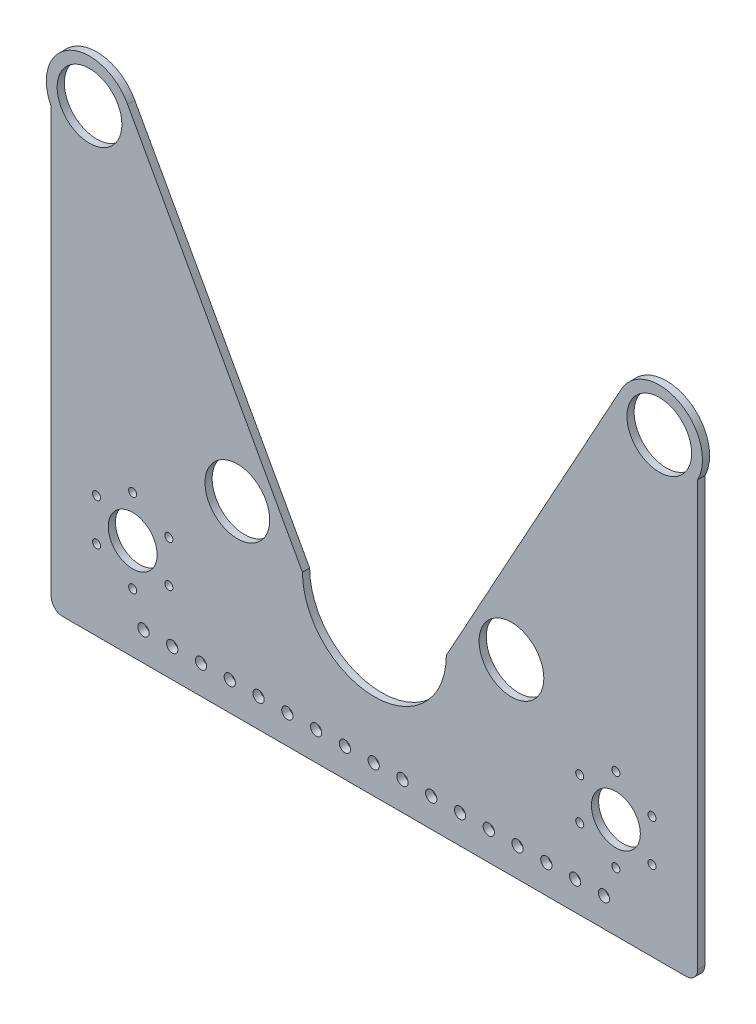
SolidWorks part; units mm, degrees
ref_plane "Front Plane" through (0, 0, 0) normal (0, 0, 1) x (1, 0, 0)
ref_plane "Top Plane" through (0, 0, 0) normal (0, 1, 0) x (1, 0, 0)
ref_plane "Right Plane" through (0, 0, 0) normal (1, 0, 0) x (0, 0, -1)
sketch "Sketch2" plane through (0, 0, 0) normal (0, 0, 1) x (1, 0, 0)
  line L0 (-142.6324, -29.9371) -> (-142.6324, -64.77)
  line L1 (142.6324, 122.4629) -> (142.6324, -29.9371)
  line L3 (31.75, 0) -> (108.9183, 140.209)
  line L4 (0, -1082.0685) -> (0, 1082.0685) construction
  line L5 (-106.68, -44.45) -> (106.68, -44.45) construction
  line L7 (0, -31.75) -> (106.68, -31.75) construction
  line L9 (-31.75, 0) -> (-108.9183, 140.209)
  line L10 (31.75, 0) -> (108.9183, 140.209)
  line L11 (142.6324, -64.77) -> (142.6324, -29.9371)
  line L33 (-106.68, -31.75) -> (0, -31.75) construction
  line L34 (-142.6324, 122.4629) -> (-142.6324, -29.9371)
  line L35 (137.5524, -69.85) -> (-137.5524, -69.85)
  arc A0 (-31.75, 0) -> (31.75, 0) centre (0, 0) ccw
  arc A1 (-108.9183, 140.209) -> (-142.6324, 122.4629) centre (-125.7268, 131.2438) ccw
  circle A2 centre (-60.4845, 12.7) radius 14.2875
  arc A3 (31.75, 0) -> (0, 31.75) centre (0, 0) ccw construction
  arc A4 (0, 31.75) -> (-31.75, 0) centre (0, 0) ccw construction
  arc A5 (137.5524, -69.85) -> (142.6324, -64.77) centre (137.5524, -64.77) ccw
  arc A6 (-137.5524, -69.85) -> (-142.6324, -64.77) centre (-137.5524, -64.77) cw
  circle A7 centre (-125.7268, 131.2438) radius 14.2875
  circle A9 centre (-60.4845, 12.7) radius 19.05 construction
  circle A10 centre (60.4845, 12.7) radius 19.05 construction
  arc A11 (108.9183, 140.209) -> (142.6324, 122.4629) centre (125.7268, 131.2438) cw
  circle A12 centre (125.7268, 131.2438) radius 14.2875
  circle A34 centre (-101.9175, -57.15) radius 2.4892
  arc A40 (-142.6324, 122.4629) -> (-108.9183, 140.209) centre (-125.7268, 131.2438) ccw construction
  arc A41 (142.6324, 122.4629) -> (108.9183, 140.209) centre (125.7268, 131.2438) cw construction
  circle A42 centre (60.4845, 12.7) radius 14.2875
  circle A43 centre (-89.2175, -57.15) radius 2.4892
  circle A44 centre (-76.5175, -57.15) radius 2.4892
  circle A45 centre (-63.8175, -57.15) radius 2.4892
  circle A46 centre (-51.1175, -57.15) radius 2.4892
  circle A47 centre (-38.4175, -57.15) radius 2.4892
  circle A48 centre (-25.7175, -57.15) radius 2.4892
  circle A49 centre (-13.0175, -57.15) radius 2.4892
  circle A50 centre (-0.3175, -57.15) radius 2.4892
  circle A51 centre (12.3825, -57.15) radius 2.4892
  circle A52 centre (25.0825, -57.15) radius 2.4892
  circle A53 centre (37.7825, -57.15) radius 2.4892
  circle A54 centre (50.4825, -57.15) radius 2.4892
  circle A55 centre (63.1825, -57.15) radius 2.4892
  circle A56 centre (75.8825, -57.15) radius 2.4892
  circle A57 centre (88.5825, -57.15) radius 2.4892
  circle A58 centre (101.2825, -57.15) radius 2.4892
  circle A69 centre (-106.68, -25.4) radius 10.795
  circle A70 centre (106.5644, -25.4) radius 10.795
  circle A74 centre (-106.68, -6.985) radius 1.778
  circle A75 centre (-90.7321, -16.1925) radius 1.778
  circle A76 centre (-90.7321, -34.6075) radius 1.778
  circle A77 centre (-106.68, -43.815) radius 1.778
  circle A78 centre (-122.6279, -34.6075) radius 1.778
  circle A79 centre (-122.6279, -16.1925) radius 1.778
  circle A81 centre (106.5644, -6.985) radius 1.778
  circle A82 centre (122.5122, -16.1925) radius 1.778
  circle A83 centre (122.5122, -34.6075) radius 1.778
  circle A84 centre (106.5644, -43.815) radius 1.778
  circle A85 centre (90.6165, -34.6075) radius 1.778
  circle A86 centre (90.6165, -16.1925) radius 1.778
  point P84 (-106.68, -25.4)
  point P98 (106.5644, -25.4)
  dimension "D7" = 131.2438
  dimension "D8" = 44.45
  dimension "D9" = 25.4
  dimension "D3" = 44.45
  dimension "D14" = 106.68
  dimension "D17" = 38.1
  dimension "D5" = 12.7
  dimension "D15" = 31.75
  dimension "D16" = 28.575
  dimension "D18" = 28.575
  dimension "D19" = 19.05
  dimension "D23" = 21.59
  dimension "D21" = 125.7268
  dimension "D27" = 3.556
  dimension "D4" = 5.08
  dimension "D11" = 35.9524
  dimension "D12" = 44.45
  dimension "D13" = 36.068
  dimension "D22" = 21.59
  dimension "D28" = 6
  dimension "D29" = 6
  dimension "D1" = 28.828
  dimension "D6" = 101.9175
  dimension "D10" = 17
  dimension "D20" = 142.6324
  dimension "D25" = 152.4
  dimension "D26" = 12.7
extrude "Boss-Extrude1" add sketch "Sketch2" along normal blind 3.175 contours A11 L3 A0 L9 A1 A58 A57 A56 A55 region at (-138.995, 46.2629, 0)
